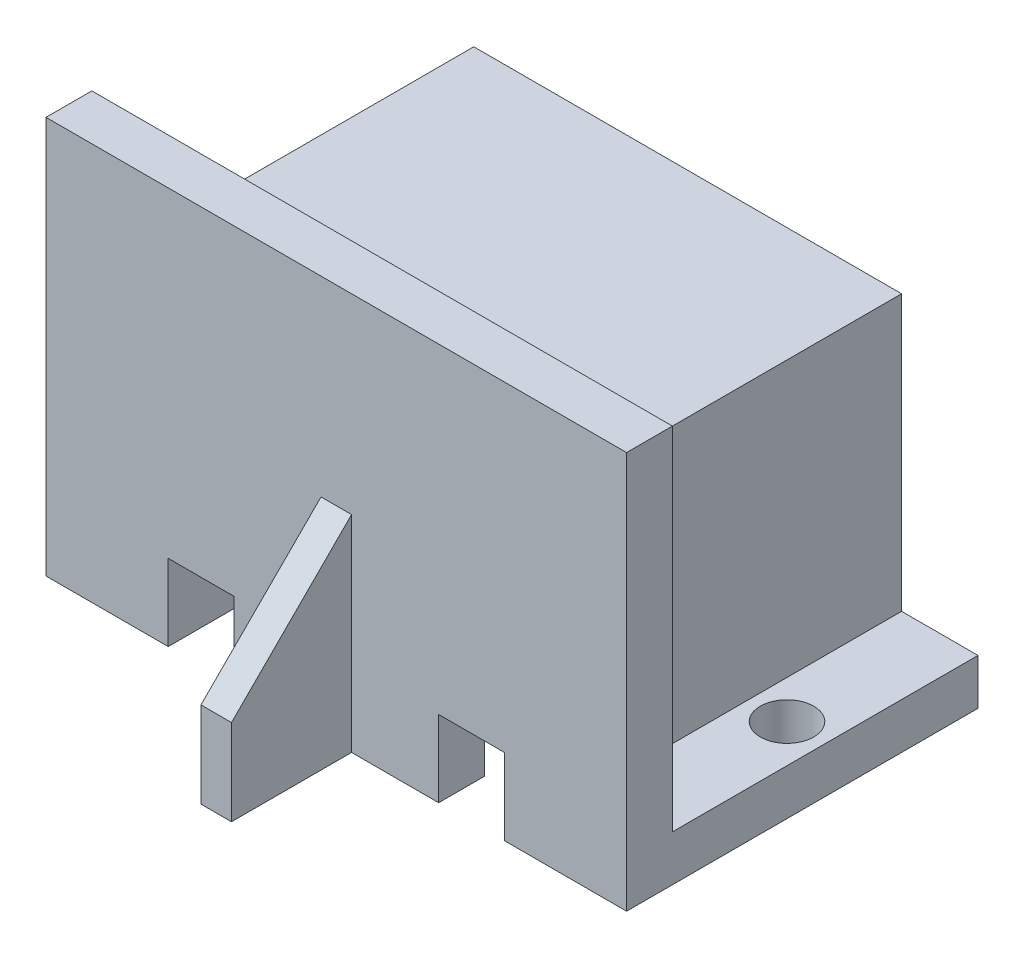
SolidWorks part; units mm, degrees
ref_plane "Front Plane" through (0, 0, 0) normal (0, 0, 1) x (1, 0, 0)
ref_plane "Top Plane" through (0, 0, 0) normal (0, 1, 0) x (1, 0, 0)
ref_plane "Right Plane" through (0, 0, 0) normal (1, 0, 0) x (0, 0, -1)
sketch "Sketch1" plane through (0, 0, 0) normal (1, 0, 0) x (0, 0, -1)
  line L1 (0, 0) -> (3, 0)
  line L2 (0, 0) -> (0, 26)
  line L3 (0, 26) -> (3, 26)
  line L4 (3, 0) -> (3, 26)
  dimension "D1" = 3
  dimension "D2" = 26
extrude "Boss-Extrude1" add sketch "Sketch1" along normal blind 38
sketch "Sketch2" plane through (0, 0, 0) normal (0, 0, 1) x (1, 0, 0)
  line L0 (38, 0) -> (0, 0) construction
  line L1 (18, 0) -> (20, 0)
  line L2 (18, 0) -> (18, 13.4839)
  line L3 (18, 13.4839) -> (20, 13.4839)
  line L4 (20, 0) -> (20, 13.4839)
  line L5 (38, 26) -> (0, 26) construction
  point P6 (19, 26)
  point P7 (19, 13.4839)
  point P10 (0, 0)
  dimension "D1" = 2
extrude "Boss-Extrude2" add sketch "Sketch2" along normal blind 20
chamfer "Chamfer1" distance 20 angle 45 1 edges at (19, 13.4839, 20)
sketch "Sketch3" plane through (0, 0, -3) normal (0, 0, -1) x (-1, 0, 0)
  line L0 (0, 0) -> (0, 26) construction
  line L1 (-38, 3) -> (0, 3)
  line L2 (-38, 3) -> (-38, 0)
  line L3 (-38, 0) -> (0, 0)
  line L4 (0, 3) -> (0, 0)
  line L5 (-38, 0) -> (0, 0) construction
  dimension "D1" = 3
extrude "Boss-Extrude3" add sketch "Sketch3" along normal blind 20
sketch "Sketch4" plane through (0, 0, 0) normal (0, -1, 0) x (1, 0, 0)
  line L0 (38, -23) -> (0, -23) construction
  line L1 (0, -23) -> (0, 0) construction
  line L2 (38, -23) -> (38, 0) construction
  circle A0 centre (2.5, -13) radius 1.75
  circle A1 centre (35.5, -13) radius 1.75
  point P4 (0, 0)
  dimension "D1" = 3.5
  dimension "D2" = 10
  dimension "D3" = 2.5
  dimension "D4" = 2.5
extrude "Cut-Extrude1" cut sketch "Sketch4" against normal through all
sketch "Sketch5" plane through (0, 3, 0) normal (0, 1, 0) x (1, 0, 0)
  line L0 (0, 23) -> (38, 23) construction
  line L1 (5, 23) -> (33, 23)
  line L2 (5, 23) -> (5, 3)
  line L3 (5, 3) -> (33, 3)
  line L4 (33, 23) -> (33, 3)
  line L5 (38, 3) -> (0, 3) construction
  circle A0 centre (2.5, 13) radius 1.75 construction
  circle A1 centre (35.5, 13) radius 1.75 construction
  dimension "D1" = 2.5
  dimension "D2" = 2.5
extrude "Boss-Extrude4" add sketch "Sketch5" along normal blind 18
sketch "Sketch6" plane through (0, 0, 0) normal (0, -1, 0) x (1, 0, 0)
  line L0 (11, -23) -> (27, -23)
  line L2 (27, -23) -> (27, -20)
  line L3 (27, -20) -> (30, -20)
  line L4 (30, -20) -> (30, -3)
  line L5 (30, -3) -> (8, -3)
  line L6 (8, -3) -> (8, -20)
  line L7 (8, -20) -> (11, -20)
  line L8 (11, -20) -> (11, -23)
  line L9 (20, 0) -> (18, 0) construction
  line L10 (33, -3) -> (33, -23) construction
  line L11 (5, -23) -> (5, -3) construction
  line L12 (0, -3) -> (5, -3) construction
  line L14 (38, -23) -> (0, -23) construction
  point P8 (19, 0)
  point P11 (19, -23)
  point P14 (0, 0)
  dimension "D1" = 16
  dimension "D2" = 3
  dimension "D3" = 3
  dimension "D4" = 3
extrude "Cut-Extrude2" cut sketch "Sketch6" against normal blind 15
sketch "Sketch7" plane through (0, 0, -3) normal (0, 0, -1) x (-1, 0, 0)
  line L0 (-30, 0) -> (-8, 0) construction
  line L1 (-30, 0) -> (-25.7004, 0)
  line L2 (-30, 0) -> (-30, 5.0023)
  line L3 (-30, 5.0023) -> (-25.7004, 5.0023)
  line L4 (-25.7004, 0) -> (-25.7004, 5.0023)
  line L5 (-30, 15) -> (-30, 0) construction
  line L6 (-12.2996, 0) -> (-8, 0)
  line L7 (-12.2996, 0) -> (-12.2996, 5.0023)
  line L8 (-12.2996, 5.0023) -> (-8, 5.0023)
  line L9 (-8, 0) -> (-8, 5.0023)
  line L10 (-8, 15) -> (-8, 0) construction
extrude "Cut-Extrude3" cut sketch "Sketch7" against normal blind 15
sketch "Sketch8" plane through (18, 0, 0) normal (-1, 0, 0) x (0, 0, 1)
  line L0 (7.8583, 5.6256) -> (7.8583, 0)
  line L1 (13.4839, 0) -> (0, 13.4839) construction
  line L2 (13.4839, 0) -> (0, 0) construction
  line L3 (7.8583, 0) -> (13.4839, 0)
  line L4 (13.4839, 0) -> (7.8583, 5.6256)
extrude "Cut-Extrude4" cut sketch "Sketch8" against normal blind 15
